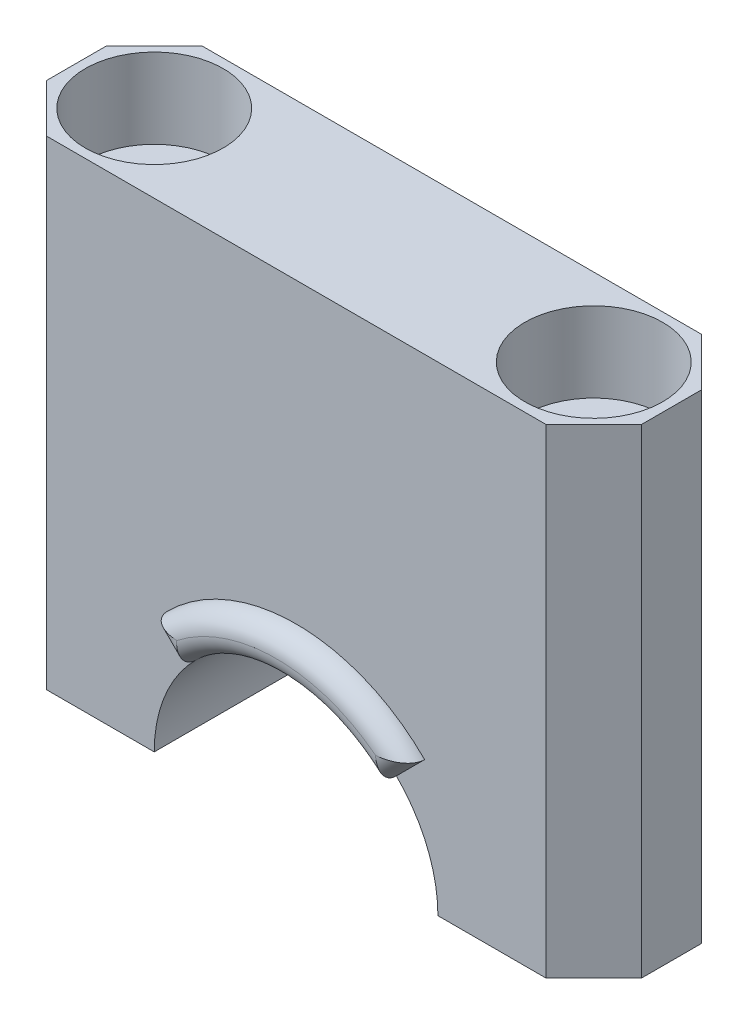
SolidWorks part; units mm, degrees
material "ABS"
ref_plane "Płaszczyzna przednia" through (0, 0, 0) normal (0, 0, 1) x (1, 0, 0)
ref_plane "Płaszczyzna górna" through (0, 0, 0) normal (0, 1, 0) x (1, 0, 0)
ref_plane "Płaszczyzna prawa" through (0, 0, 0) normal (1, 0, 0) x (0, 0, -1)
sketch "Szkic1" plane through (0, 0, 0) normal (0, 1, 0) x (1, 0, 0)
  line L0 (0, -3.9) -> (0, 3.9) construction
  line L1 (12.5, 3.9) -> (-12.5, 3.9)
  line L2 (14.9, 0) -> (-14.9, 0) construction
  line L3 (-14.9, -1.5) -> (-14.9, 1.5)
  line L4 (-14.9, 1.5) -> (-12.5, 3.9)
  line L5 (14.9, 1.5) -> (14.9, -1.5)
  line L6 (14.9, 1.5) -> (12.5, 3.9)
  line L7 (-14.9, -1.5) -> (-12.5, -3.9)
  line L8 (12.5, -3.9) -> (-12.5, -3.9)
  line L9 (14.9, -1.5) -> (12.5, -3.9)
  line L10 (0, 0) -> (-11, 0) construction
  circle A0 centre (-11, 0) radius 2.1
  circle A1 centre (11, 0) radius 2.1
  point P4 (0, 0)
  point P9 (0, 3.9)
  point P12 (0, 0)
  point P15 (-14.9, 0)
  point P18 (14.9, 0)
  dimension "D7" = 4.2
  dimension "D1" = 7.8
  dimension "D2" = 29.8
  dimension "D3" = 3
  dimension "D4" = 25
  dimension "D5" = 3
  dimension "D6" = 11
extrude "Dodanie-wyciągnięcie1" add sketch "Szkic1" against normal blind 24
ref_plane "Płaszczyzna1" through (0, 0, -3.9) normal (0, 0, -1) x (-1, 0, 0)
sketch "Szkic2" plane through (0, 0, -3.9) normal (0, 0, -1) x (-1, 0, 0)
  line L0 (0, 0) -> (0, -24) construction
  line L1 (-12.5, -24) -> (12.5, -24) construction
  line L2 (-7.1, -24) -> (7.1, -24)
  arc A0 (7.1, -24) -> (-7.1, -24) centre (0, -24) ccw
  dimension "D2" = 7.1
  dimension "D1" = 24
extrude "Wytnij-wyciągnięcie1" cut sketch "Szkic2" against normal up to next
sketch "Szkic3" plane through (0, 0, 0) normal (0, 1, 0) x (1, 0, 0)
  line L0 (0, -4.29) -> (0, 4.29) construction
  circle A0 centre (-11, 0) radius 3.45
  circle A1 centre (11, 0) radius 3.45
  dimension "D1" = 6.9
extrude "Wytnij-wyciągnięcie2" cut sketch "Szkic3" against normal blind 4
sketch "Szkic4" plane through (0, 0, 3.9) normal (0, 0, 1) x (1, 0, 0)
  line L0 (-7.1, -24) -> (-7.1, -14.182) construction
  line L1 (-7.1, -14.182) -> (7.1, -14.182) construction
  line L2 (7.1, -14.182) -> (7.1, -24) construction
  line L3 (0, -14.9) -> (0, -14.182) construction
  line L4 (5.0205, -18.9795) -> (6.4347, -17.5653)
  line L5 (-5.0205, -18.9795) -> (-6.4347, -17.5653)
  line L6 (-5.0205, -18.9795) -> (-6.4347, -17.5653)
  line L7 (0, -24) -> (-5.0205, -18.9795) construction
  line L8 (0, -24) -> (0, -16.9) construction
  line L9 (0, -24) -> (5.0205, -18.9795) construction
  line L10 (6.4347, -17.5653) -> (7.1, -16.9) construction
  line L11 (-6.4347, -17.5653) -> (-7.1, -16.9) construction
  line L12 (0, -16.9) -> (0, -14.9) construction
  arc A0 (-5.0205, -18.9795) -> (5.0205, -18.9795) centre (0, -24) cw
  arc A1 (7.1, -24) -> (-7.1, -24) centre (0, -24) ccw construction
  arc A2 (-6.4347, -17.5653) -> (6.4347, -17.5653) centre (0, -24) cw
  arc M7 (-7.1, -24) -> (7.1, -24) centre (0, -24) cw
  dimension "D1" = 45
  dimension "D2" = 45
  dimension "D3" = 2
extrude "Dodanie-wyciągnięcie2" add sketch "Szkic4" along normal blind 1 contours A2 L5 L4 M7 region at (0, -16.6704, 3.9)
fillet "Zaokrąglenie2" radius 1 4 edges at (-5.7276, -18.2724, 4.9) (5.7276, -18.2724, 4.9) (0, -14.9, 4.9) (0, -16.9, 4.9)
mirror "Lustro3" about plane through (0, 0, 0) normal (0, 0, 1) of "Zaokrąglenie2", "Dodanie-wyciągnięcie2"
equation "\"Tolerance\"= 0.1"
equation "\"Depth\"=10"
equation "\"D1@Szkic1\"=\"RailZ\"-\"Tolerance\"*2"
equation "\"Width\"= 16"
equation "\"D2@Szkic1\"=\"Diameter\"+\"RailX\"*2-\"Tolerance\"*2"
equation "\"Diameter\"= 14"
equation "\"RailX\"= 8"
equation "\"RailZ\"= 8"
equation "\"D3@Szkic1\"=\"RailZ\"*0.4-\"Tolerance\"*2"
equation "\"D4@Szkic1\"=\"Diameter\"+2*0.7*\"RailX\"-\"Tolerance\"*2"
equation "\"D5@Szkic1\"=\"RailZ\"*0.4-\"Tolerance\"*2"
equation "\"D6@Szkic1\"=\"Diameter\"/2+\"RailX\"/2"
equation "\"Hight\"=24"
equation "\"D1@Szkic2\"=\"Hight\""
equation "\"D2@Szkic2\"=\"Diameter\"/2+\"Tolerance\""
equation "\"D1@Dodanie-wyciągnięcie1\"=\"Hight\""
